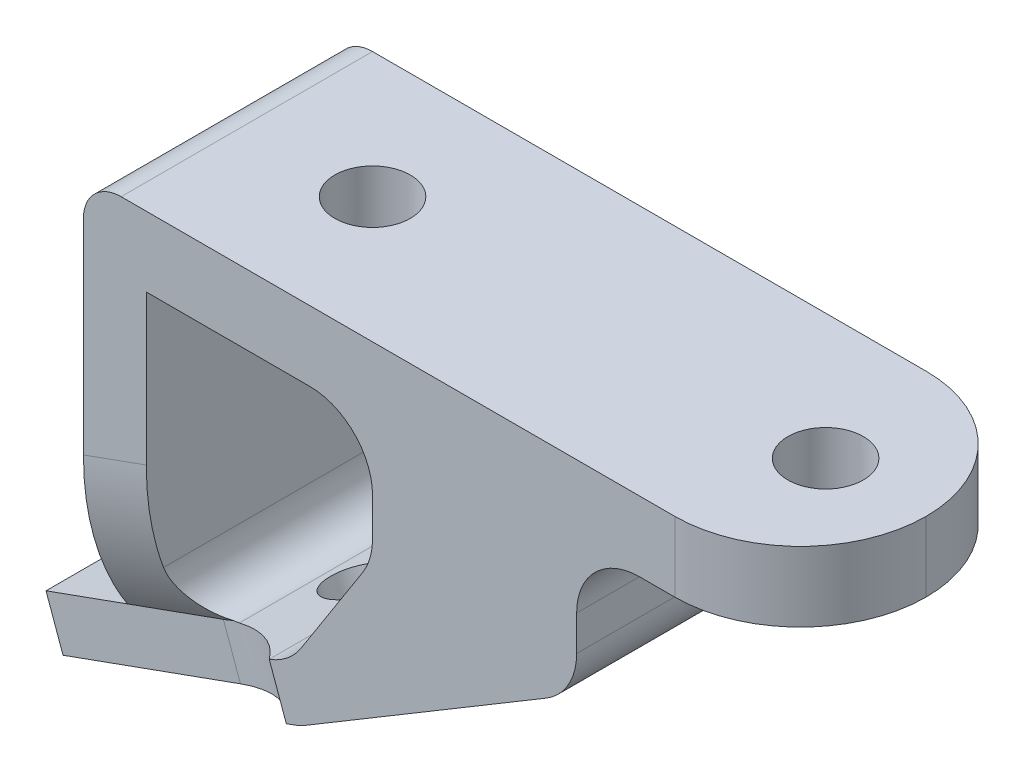
SolidWorks part; units mm, degrees
ref_plane "Plan de face" through (0, 0, 0) normal (0, 0, 1) x (1, 0, 0)
ref_plane "Plan de dessus" through (0, 0, 0) normal (0, 1, 0) x (1, 0, 0)
ref_plane "Plan de droite" through (0, 0, 0) normal (1, 0, 0) x (0, 0, -1)
sketch "Esquisse1" plane through (0, 0, 0) normal (0, 0, 1) x (1, 0, 0)
  line L0 (-93.1144, -46.1084) -> (78.8856, 15.8916) construction
  line L1 (78.8856, 15.8916) -> (-93.1144, 15.8916) construction
  line L2 (-93.1144, 15.8916) -> (-93.1144, -46.1084) construction
  line L3 (-75.3768, -39.7146) -> (-95.4209, 15.8916) construction
  line L4 (-81.9385, -21.5112) -> (-60.0238, -13.6117)
  line L6 (-62.0345, -10.0845) -> (-71.8183, -13.6113)
  line L7 (-83.2949, -17.7482) -> (-81.9385, -21.5112)
  line L8 (23.4018, -4.1084) -> (16.1925, 15.8916) construction
  line L10 (-53.8183, 2.2963) -> (-53.8183, 5.3271)
  line L11 (-53.8183, 15.8916) -> (-37.5815, 15.8916)
  line L12 (-37.5815, 5.3271) -> (-37.5815, 2.5357)
  line L13 (-59.5183, -8.0755) -> (-54.6065, -0.3984)
  line L15 (-37.5815, 15.8916) -> (-19.7738, 15.8916)
  line L16 (-19.7738, 15.8916) -> (-19.7738, 10.3271)
  line L17 (-19.7738, 10.3271) -> (-32.5815, 10.3271)
  line L18 (-53.8183, 15.8916) -> (-71.8183, 15.8916)
  line L20 (-71.8183, 10.3271) -> (-58.8183, 10.3271)
  line L21 (-59.1533, -13.1993) -> (-40.0155, -1.7556)
  line L22 (-71.8183, 15.8916) -> (-76.8183, 15.8916)
  line L23 (-76.8183, 15.8916) -> (-76.8183, -15.4136)
  line L25 (-71.8183, -13.6113) -> (-71.8183, 10.3271)
  line L26 (-76.8183, -15.4136) -> (-83.2949, -17.7482)
  arc A3 (-32.5815, 10.3271) -> (-37.5815, 5.3271) centre (-32.5815, 5.3271) ccw
  arc A4 (-58.8183, 10.3271) -> (-53.8183, 5.3271) centre (-58.8183, 5.3271) cw
  arc A5 (-54.6065, -0.3984) -> (-53.8183, 2.2963) centre (-58.8183, 2.2963) ccw
  arc A6 (-59.5183, -8.0755) -> (-62.0345, -10.0845) centre (-63.73, -5.3808) cw
  arc A7 (-60.0238, -13.6117) -> (-59.1533, -13.1993) centre (-61.7193, -8.908) ccw
  arc A8 (-40.0155, -1.7556) -> (-37.5815, 2.5357) centre (-42.5815, 2.5357) ccw
  point P5 (-81.9385, -21.5112)
  point P26 (-59.0783, -13.2709)
  point P31 (-37.5815, 10.3271)
  point P36 (-60.4347, -9.5079)
  dimension "D13" = 5
  dimension "D17" = 5
  dimension "D1" = 172
  dimension "D2" = 62
  dimension "D3" = 90
  dimension "D4" = 70.178
  dimension "D5" = 19.822
  dimension "D6" = 182.8333
  dimension "D7" = 90
  dimension "D8" = 19.35
  dimension "D9" = 90
  dimension "D10" = 24.3
  dimension "D11" = 4
  dimension "D12" = 90
  dimension "D14" = 90
  dimension "D15" = 105
  dimension "D16" = 20
extrude "Boss.-Extru.1" add sketch "Esquisse1" along normal blind 20
fillet "Congé1" radius 10 2 edges at (-19.7738, 13.1093, 0) (-19.7738, 13.1093, 20)
sketch "Esquisse4" plane through (0, 15.8916, 0) normal (0, 1, 0) x (1, 0, 0)
  line L0 (-29.7738, 0) -> (-76.8183, 0) construction
  circle A0 centre (-63.8183, -10) radius 3
  circle A1 centre (-27.7738, -10) radius 3
  dimension "D1" = 8
  dimension "D4" = 6
  dimension "D2" = 8
  dimension "D3" = 10
extrude "Enlèv. mat.-Extru.1" cut sketch "Esquisse4" against normal blind 10
sketch "Esquisse5" plane through (-3.9164, 10.865, 0) normal (-0.3391, 0.9407, 0) x (0.9407, 0.3391, 0)
  line L0 (-84.378, -20) -> (-84.378, 0) construction
  line L1 (-84.378, -3.5) -> (-61.7785, -3.5)
  line L3 (-84.378, -16.5) -> (-61.7785, -16.5)
  line L5 (-61.7785, -20) -> (-61.7785, 0) construction
  line L6 (-61.7785, -20) -> (-72.1785, -20) construction
  line L7 (-84.378, -3.5) -> (-84.378, 0)
  line L8 (-84.378, 0) -> (-61.7785, 0)
  line L9 (-61.7785, 0) -> (-61.7785, -3.5)
  line L10 (-84.378, -20) -> (-84.378, -16.5)
  line L11 (-61.7785, -16.5) -> (-61.7785, -20)
  line L12 (-61.7785, -20) -> (-84.378, -20)
  circle A0 centre (-64.728, -10) radius 2.5
  circle A1 centre (-79.728, -10) radius 2.5
  dimension "D1" = 13
  dimension "D2" = 22.5995
  dimension "D3" = 3.5
  dimension "D4" = 10
  dimension "D5" = 10
  dimension "D6" = 4.65
  dimension "D7" = 15
extrude "Enlèv. mat.-Extru.2" cut sketch "Esquisse5" against normal blind 10
fillet "Congé2" radius 10 2 edges at (-61.3563, -11.966, 3.5) (-61.3563, -11.966, 16.5)
fillet "Congé3" radius 20 2 edges at (-74.3183, -14.5124, 0) (-74.3183, -14.5124, 20)
fillet "Congé4" radius 3 1 edges at (-71.8183, -13.6113, 10)
fillet "Congé5" radius 3 1 edges at (-76.8183, 15.8916, 10)
